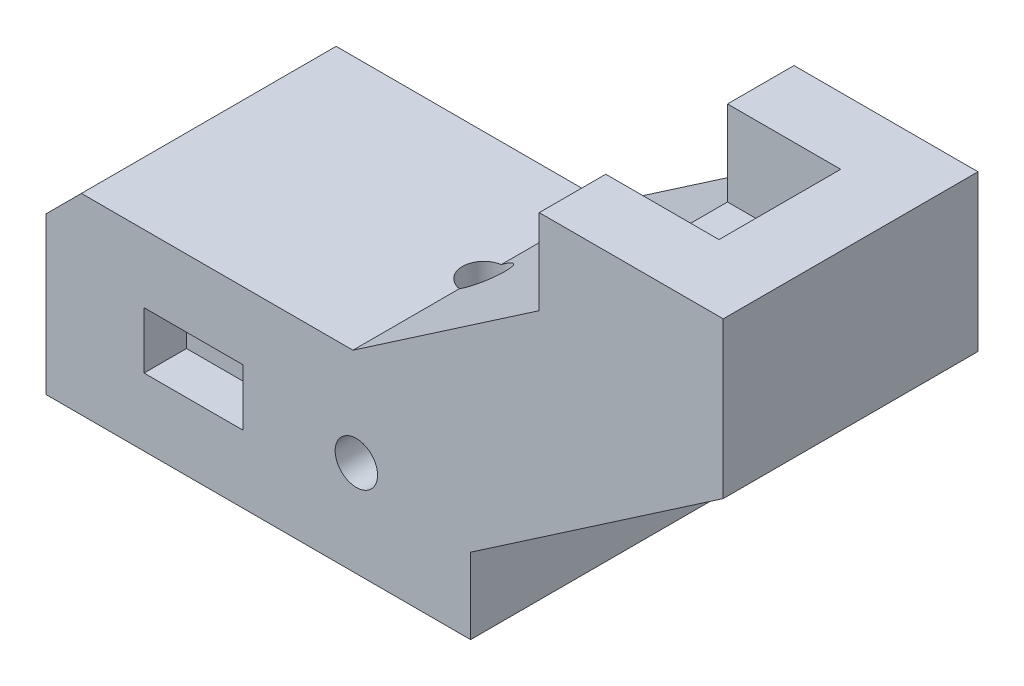
SolidWorks part; units mm, degrees
ref_plane "Front Plane" through (0, 0, 0) normal (0, 0, 1) x (1, 0, 0)
ref_plane "Top Plane" through (0, 0, 0) normal (0, 1, 0) x (1, 0, 0)
ref_plane "Right Plane" through (0, 0, 0) normal (1, 0, 0) x (0, 0, -1)
sketch "Sketch1" plane through (0, 0, 0) normal (0, 0, 1) x (1, 0, 0)
  line L0 (0, 6) -> (5, 6)
  line L1 (5, 6) -> (5, -5)
  line L2 (-20.6795, -22.5563) -> (-49.0563, -22.5563)
  line L4 (-49.0563, -22.5563) -> (-60.5563, -11.0563)
  line L5 (-60.5563, -11.0563) -> (-46.4142, 3.0858)
  line L6 (-46.4142, 3.0858) -> (-34.3284, -9)
  line L7 (-34.3284, -9) -> (-21.1642, -9)
  line L8 (-8, -9) -> (-8, 0) construction
  line L9 (0, 0) -> (-30, 0) construction
  line L10 (-8, 0) -> (0, 0)
  line L11 (0, 0) -> (0, 6)
  line L12 (-39.25, -1.25) -> (-54.8063, -16.8063) construction
  line L13 (-45, 4.5) -> (-46.4142, 3.0858) construction
  line L14 (-33.5, -7) -> (-54.8063, -16.8063) construction
  line L15 (-54.8063, -16.8063) -> (-45, 4.5) construction
  line L16 (-8, 0) -> (-21.1642, -9)
  line L17 (5, -5) -> (-20.6795, -22.5563)
  line L18 (-8, -9) -> (-8, -17) construction
  line L19 (-33.5, -7) -> (-45, 4.5) construction
  line L20 (5, -17) -> (-8, -17) construction
  line L21 (-33.5, -7) -> (-45, 4.5) construction
  line L22 (-8, -17) -> (-20.6795, -22.5563) construction
  line L23 (5, -5) -> (5, -17) construction
  line L24 (-21.1642, -9) -> (-8, -9) construction
  line L25 (0, 0) -> (-30, 0) construction
  dimension "D1" = 2
  dimension "D2" = 8
  dimension "D3" = 2
  dimension "D4" = 20
  dimension "D5" = 8
  dimension "D6" = 5
  dimension "D7" = 11
extrude "Boss-Extrude1" add sketch "Sketch1" against normal blind 13 and the other way blind 5
sketch "Sketch2" plane through (0, 0, 0) normal (0, 1, 0) x (1, 0, 0)
  circle A0 centre (-3, 3.95) radius 1.5
  circle A1 centre (-3, 3.95) radius 1.5 construction
extrude "Cut-Extrude1" cut sketch "Sketch2" against normal through all
sketch "Sketch4" plane through (0, 0, 0) normal (0, 1, 0) x (1, 0, 0)
  line L0 (0, -5) -> (0, 13) construction
  line L1 (-8, -5) -> (0, -5)
  line L2 (-8, -5) -> (-8, -0.3)
  line L3 (-8, -0.3) -> (0, -0.3)
  line L4 (0, -5) -> (0, -0.3)
  line L5 (0, 0) -> (-30, 0) construction
  line L6 (-8, 13) -> (0, 13)
  line L7 (-8, 13) -> (-8, 8.3)
  line L8 (-8, 8.3) -> (0, 8.3)
  line L9 (0, 13) -> (0, 8.3)
  line L10 (-8, -5) -> (-8, 13) construction
  line L11 (0, -5) -> (-8, -5) construction
  dimension "D1" = 0.3
extrude "Boss-Extrude2" add sketch "Sketch4" along normal up to surface (6 mm away) up to face at (2.5, 6, -4)
sketch "Sketch5" plane through (0, 0, 0) normal (0, 1, 0) x (1, 0, 0)
  line L0 (-1.2679, 0.95) -> (-4.7321, 0.95)
  line L1 (-4.7321, 0.95) -> (-6.4641, 3.95)
  line L2 (-6.4641, 3.95) -> (-4.7321, 6.95)
  line L3 (-4.7321, 6.95) -> (-1.2679, 6.95)
  line L4 (-1.2679, 6.95) -> (0.4641, 3.95)
  line L5 (0.4641, 3.95) -> (-1.2679, 0.95)
  circle A0 centre (-3, 3.95) radius 3.4641 construction
  circle A1 centre (-3, 3.95) radius 1.5 construction
  dimension "D1" = 6
extrude "Cut-Extrude3" cut sketch "Sketch5" against normal through all from offset 5 offset against normal yes
sketch "Sketch6" plane through (0, 0, 5) normal (0, 0, 1) x (1, 0, 0)
  line L2 (-60.5563, -11.0563) -> (-49.0563, -22.5563) construction
  line L10 (-54.8063, -16.8063) -> (-30.3048, 7.6952) construction
  line L11 (-33.5, -7) -> (-45, 4.5) construction
  line L12 (-53.1, -15.1) -> (-25.85, -15.1) construction
  line L13 (-45.997, -12) -> (-25.85, -12) construction
  line L14 (-45.997, -12) -> (-45.997, -18.2) construction
  line L15 (-45.997, -18.2) -> (-25.85, -18.2) construction
  line L16 (-25.85, -12) -> (-25.85, -18.2) construction
  line L17 (-53.1, -15.1) -> (-60.85, -15.1) construction
  line L18 (0, 0) -> (-30, 0) construction
  line L19 (-21.1642, -9) -> (-34.3284, -9) construction
  line L20 (-42.85, -22.5563) -> (-49.0563, -22.5563)
  line L21 (-49.0563, -22.5563) -> (-20.6795, -22.5563) construction
  line L22 (-49.0563, -22.5563) -> (-60.5563, -11.0563)
  line L23 (-46.4142, 3.0858) -> (-60.5563, -11.0563) construction
  line L24 (-60.5563, -11.0563) -> (-46.4142, 3.0858)
  line L25 (-46.4142, 3.0858) -> (-45.85, 2.5216)
  line L26 (-34.3284, -9) -> (-46.4142, 3.0858) construction
  line L27 (-42.85, -9) -> (-42.85, -22.5563)
  line L28 (-34.3284, -9) -> (-42.85, -9)
  line L29 (-46.4142, 3.0858) -> (-34.3284, -9)
  circle A0 centre (-53.1, -15.1) radius 7.75 construction
  line M24 (-34.3284, -9) -> (-46.4142, 3.0858)
  line M25 (-46.4142, 3.0858) -> (-60.5563, -11.0563)
  line M26 (-60.5563, -11.0563) -> (-49.0563, -22.5563)
  line M27 (-49.0563, -22.5563) -> (-20.6795, -22.5563)
  dimension "D1" = 15.5
  dimension "D2" = 6.2
  dimension "D3" = 35
  dimension "D4" = 3
  dimension "D5" = 17
extrude "Cut-Extrude4" cut sketch "Sketch6" against normal through all contours L28 L27 M24 M25 M26 M27 region at (-48.1741, -10.2401, 5)
ref_axis "Axis1" through (-3, -5, -3.95) along (0, 1, 0)
ref_plane "Plane1" through (0, 0, -3.95) normal (0, 0, 1) x (1, 0, 0)
sketch "Sketch7" plane through (0, 0, -3.95) normal (0, 0, 1) x (1, 0, 0)
  line L0 (-45.997, -12) -> (-45.997, -18.2) construction
  line L1 (-25.85, -12) -> (-25.85, -18.2) construction
  line L4 (-45.997, -18.2) -> (-25.85, -18.2) construction
  line L5 (-45.997, -12) -> (-45.997, -15.1)
  line L6 (-25.85, -12.35) -> (-25.85, -15.1) construction
  line L7 (-45.997, -12) -> (-39.7903, -12)
  line L8 (-45.997, -15.1) -> (-25.85, -15.1)
  line L9 (-45.997, -18.2) -> (-25.85, -18.2) construction
  line L10 (-39.7903, -12) -> (-25.85, -12) construction
  line L11 (-25.85, -15.1) -> (-25.85, -18.2) construction
  line L12 (-45.997, -15.1) -> (-45.997, -18.2) construction
  line L13 (-53.2914, -15.1) -> (-45.997, -15.1) construction
  line L14 (-38.2903, -12.35) -> (-25.85, -12.35)
  line L15 (-46.2903, -11.4) -> (-43.2903, -11.4)
  line L16 (-43.2903, -11.4) -> (-43.2903, -12)
  line L17 (-43.2903, -12) -> (-39.7903, -12)
  line L18 (-39.7903, -12) -> (-38.2903, -12.35)
  line L19 (-25.85, -12) -> (-25.85, -12.35) construction
  line L20 (-53.1, -15.1) -> (-25.85, -15.1) construction
  line L21 (-25.85, -12.35) -> (-24.85, -12.85)
  line L22 (-24.85, -12.85) -> (-24.85, -15.1)
  line L23 (-24.85, -15.1) -> (-25.85, -15.1)
  circle A2 centre (-53.1, -15.1) radius 7.75 construction
  dimension "D1" = 3.5
  dimension "D2" = 3
  dimension "D3" = 3.7
  dimension "D4" = 3.1
  dimension "D5" = 2.75
  dimension "D6" = 1.5
  dimension "D7" = 1
  dimension "D8" = 0.5
revolve "Cut-Revolve1" cut sketch "Sketch7" angle 360 about L8 region at (-35.7517, -13.6677, -3.95)
chamfer "Chamfer1" distance 2.5 angle 45 1 edges at (-42.85, -9, -4)
sketch "Sketch8" plane through (0, 0, 5) normal (0, 0, 1) x (1, 0, 0)
  line L0 (-21.1642, -9) -> (-20.6795, -22.5563) construction
  circle A0 centre (-20.9219, -15.7782) radius 1.5
  dimension "D1" = 3
extrude "Cut-Extrude5" cut sketch "Sketch8" against normal through all
ref_plane "Plane2" through (0, 0, -4) normal (0, 0, 1) x (1, 0, 0)
sketch "Sketch10" plane through (0, 0, 5) normal (0, 0, 1) x (1, 0, 0)
  line L0 (-20.9219, -15.7782) -> (-28.9219, -15.7782) construction
  line L1 (-35.9219, -13.7782) -> (-28.9219, -13.7782)
  line L2 (-35.9219, -13.7782) -> (-35.9219, -17.7782)
  line L3 (-35.9219, -17.7782) -> (-28.9219, -17.7782)
  line L4 (-28.9219, -13.7782) -> (-28.9219, -17.7782)
  circle A1 centre (-20.9219, -15.7782) radius 1.5 construction
  point P6 (0, 0)
  dimension "D1" = 7
  dimension "D2" = 8
  dimension "D3" = 4
extrude "Cut-Extrude7" cut sketch "Sketch10" against normal blind 3
mirror "Mirror1" about plane through (0, 0, -4) normal (0, 0, 1) of "Cut-Extrude7"
sketch "Sketch11" plane through (0, -22.5563, 0) normal (0, -1, 0) x (1, 0, 0)
  line L0 (-35.9219, -2) -> (-35.9219, 5) construction
  line L1 (-35.9219, -2) -> (-28.9219, -2)
  line L2 (-35.9219, -2) -> (-35.9219, -6)
  line L3 (-35.9219, -6) -> (-28.9219, -6)
  line L4 (-28.9219, -2) -> (-28.9219, -6)
  line L6 (-42.85, 5) -> (-20.6795, 5) construction
  line L7 (-20.6795, 5) -> (-20.6795, -13) construction
  line L8 (-20.6795, -4) -> (-28.9219, -4) construction
  line L9 (-35.9219, 5) -> (-28.9219, 5) construction
  line L10 (-28.9219, 5) -> (-28.9219, -2) construction
  point P7 (0, 0)
  point P13 (0, 0)
  dimension "D2" = 4
extrude "Cut-Extrude8" cut sketch "Sketch11" against normal blind 3
sketch "Sketch12" plane through (0, 0, 5) normal (0, 0, 1) x (1, 0, 0)
  line L0 (-20.6795, -22.5563) -> (-12.85, -22.5563)
  line L1 (-12.85, -22.5563) -> (-12.85, -17.2035)
  line L2 (-20.6795, -22.5563) -> (5, -5) construction
  line L3 (-12.85, -17.2035) -> (-20.6795, -22.5563)
  line L4 (-42.85, -11.5) -> (-42.85, -22.5563) construction
  dimension "D1" = 30
extrude "Boss-Extrude3" add sketch "Sketch12" against normal up to surface (18 mm away) up to face at (-19.4219, -15.7782, -13)
sketch "Sketch13" plane through (0, -22.5563, 0) normal (0, -1, 0) x (1, 0, 0)
  line L0 (-20.9219, -4) -> (-12.85, -4) construction
  line L1 (-12.85, -13) -> (-12.85, 5) construction
  line L2 (-20.9219, -4) -> (-20.9219, 5) construction
  line L3 (-42.85, 5) -> (-12.85, 5) construction
  line L4 (-19.4219, 5) -> (-22.4219, 5) construction
  line L5 (-19.4219, 5) -> (-22.4219, 5) construction
  line L6 (-22.4219, 5) -> (-22.4219, -4) construction
  circle A0 centre (-20.9219, -4) radius 1.5
extrude "Cut-Extrude9" cut sketch "Sketch13" against normal through all
